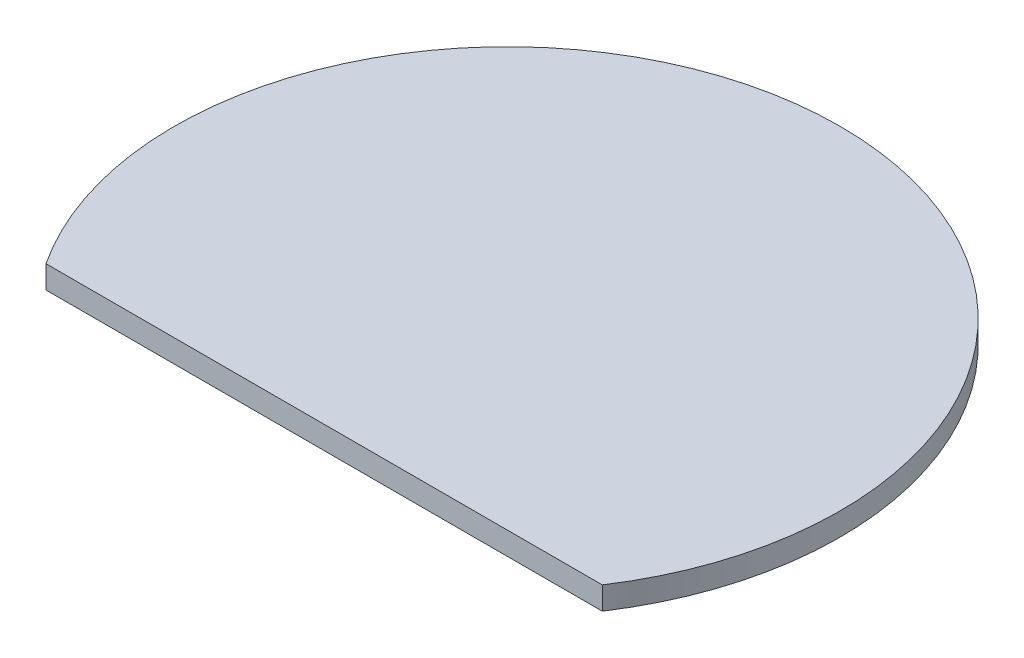
SolidWorks part; units mm, degrees
ref_plane "Front Plane" through (0, 0, 0) normal (0, 0, 1) x (1, 0, 0)
ref_plane "Top Plane" through (0, 0, 0) normal (0, 1, 0) x (1, 0, 0)
ref_plane "Right Plane" through (0, 0, 0) normal (1, 0, 0) x (0, 0, -1)
sketch "Sketch1" plane through (0, 0, 0) normal (0, 1, 0) x (1, 0, 0)
  line L0 (-12.195, -8.0276) -> (12.195, -8.0276)
  arc A0 (12.195, -8.0276) -> (-12.195, -8.0276) centre (0, 0) ccw
  dimension "D1" = 29.2
  dimension "D2" = 24.39
extrude "Boss-Extrude1" add sketch "Sketch1" along normal blind 1
